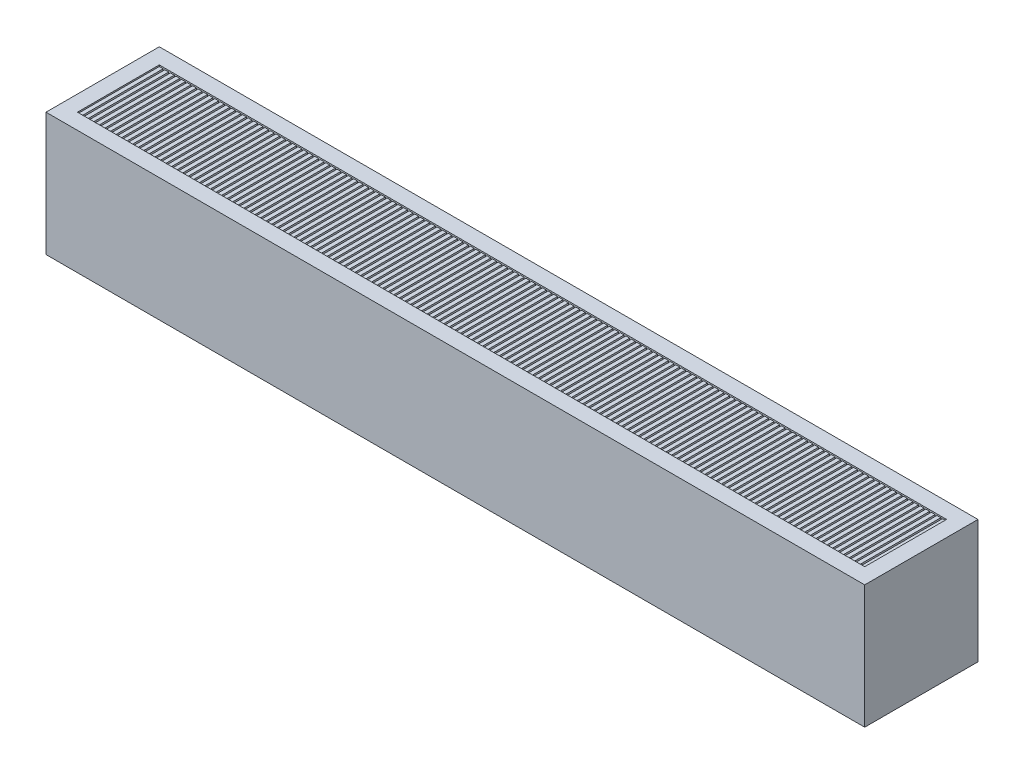
SolidWorks part; units mm, degrees
ref_plane "Front Plane" through (0, 0, 0) normal (0, 0, 1) x (1, 0, 0)
ref_plane "Top Plane" through (0, 0, 0) normal (0, 1, 0) x (1, 0, 0)
ref_plane "Right Plane" through (0, 0, 0) normal (1, 0, 0) x (0, 0, -1)
sketch "Sketch1" plane through (0, 0, 0) normal (0, 1, 0) x (1, 0, 0)
  line L0 (0, 0) -> (737, 0)
  line L1 (737, 0) -> (737, 102)
  line L2 (737, 102) -> (0, 102)
  line L3 (0, 102) -> (0, 0)
  dimension "D1" = 737
  dimension "D2" = 102
extrude "Boss-Extrude1" add sketch "Sketch1" along normal blind 111 contours L3 L0 L1 L2
sketch "Sketch2" plane through (0, 111, 0) normal (0, 1, 0) x (1, 0, 0)
  line L2 (14.1421, 87.8579) -> (14.1421, 14.1421)
  line L3 (0, 0) -> (737, 0) construction
  line L4 (368.5, 102) -> (368.5, 0) construction
  line L5 (737, 102) -> (0, 102) construction
  line L7 (722.8579, 87.8579) -> (722.8579, 14.1421)
  line L9 (14.1421, 87.8579) -> (722.8579, 87.8579)
  line L10 (14.1421, 14.1421) -> (722.8579, 14.1421)
  line L11 (0, 102) -> (0, 0)
  line L12 (737, 102) -> (737, 0)
extrude "Cut-Extrude1" cut sketch "Sketch2" against normal blind 12 contours L4 L9 L2 L10 | L9 L4 L10 L7 region at (191.3211, 111, -51) region at (545.6789, 111, -51)
sketch "Sketch10" plane through (0, 0, -87.8579) normal (0, 0, 1) x (1, 0, 0)
  line L0 (14.1421, 99) -> (14.1421, 109.7173)
  line L2 (14.1421, 109.7173) -> (17.6106, 109.7173)
  line L3 (17.6106, 109.7173) -> (17.6106, 99)
  line L4 (14.1421, 99) -> (722.8579, 99) construction
  line L5 (14.1421, 99) -> (17.6106, 99)
extrude "Boss-Extrude3" add sketch "Sketch10" along normal blind 74
pattern_linear "LPattern1" count 142 spacing 5 along (1, 0, 0) of "Boss-Extrude3"
